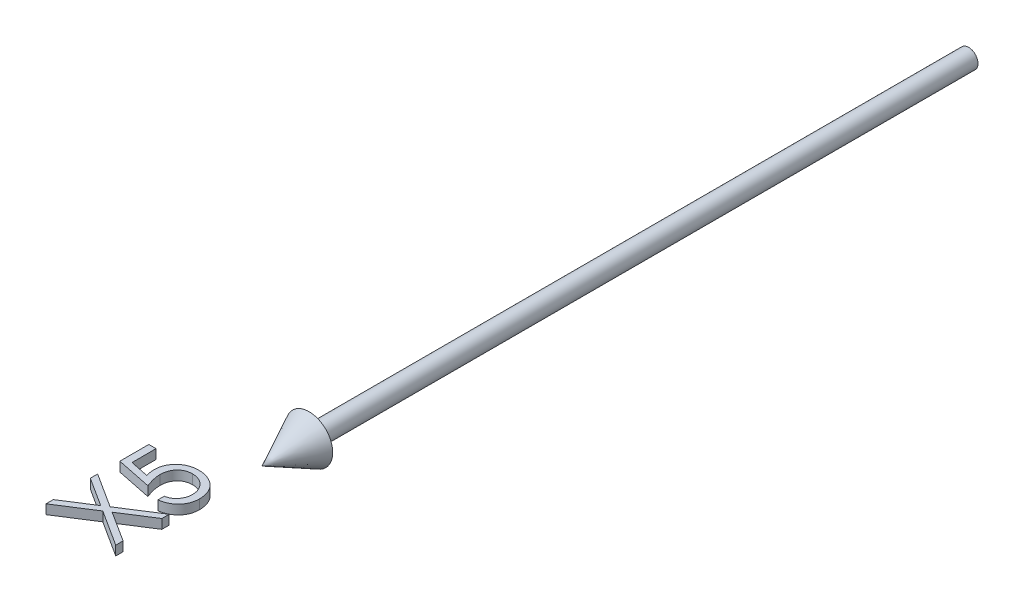
SolidWorks part; units mm, degrees
ref_plane "Front Plane" through (0, 0, 0) normal (0, 0, 1) x (1, 0, 0)
ref_plane "Top Plane" through (0, 0, 0) normal (0, 1, 0) x (1, 0, 0)
ref_plane "Right Plane" through (0, 0, 0) normal (1, 0, 0) x (0, 0, -1)
sketch "Sketch2" plane through (0, 0, 0) normal (0, 1, 0) x (1, 0, 0)
  line L0 (0, 41.95) -> (0, -114.4521) construction
  line L1 (-36.8894, 0) -> (41.4965, 0) construction
  line L2 (0, -150) -> (5, -140)
  line L3 (5, -140) -> (2, -140)
  line L4 (2, -140) -> (2, 0)
  line L5 (2, 0) -> (0, 0)
  line L6 (0, 0) -> (0, -150)
  dimension "D1" = 150
  dimension "D2" = 2
  dimension "D3" = 10
  dimension "D4" = 5
revolve "Revolve1" add sketch "Sketch2" angle 360 about L0
sketch "Sketch3" plane through (0, 0, 0) normal (0, 1, 0) x (1, 0, 0)
  line L0 (0, -157.5) -> (0, -258.0487) construction
  line L1 (-29.1507, 0) -> (29.9298, 0) construction
  text T0 "X5\r\n\r\n" font "Century Gothic" height 15
  point P6 (0, -224.404)
  point P7 (0, -158.6218)
  point P8 (0, -258.0487)
  dimension "D1" = 157.5
extrude "Boss-Extrude1" add sketch "Sketch3" against normal blind 1 and the other way blind 1 separate body
equation "\"D1@Sketch2\"=\"frame_arrow_length\""
equation "\"D2@Sketch2\"=\"frame_arrow_odA\"/2"
equation "\"D4@Sketch2\"=\"frame_arrow_head_od\""
equation "\"D3@Sketch2\"=\"frame_arrow_head_length\""
equation "\"frame_arrow_length\"=150"
equation "\"frame_arrow_head_length\"=10"
equation "\"frame_arrow_head_od\"=5"
equation "\"frame_arrow_odA\"=4"
equation "\"D1@Sketch3\"=\"frame_arrow_length\"*1.05"
